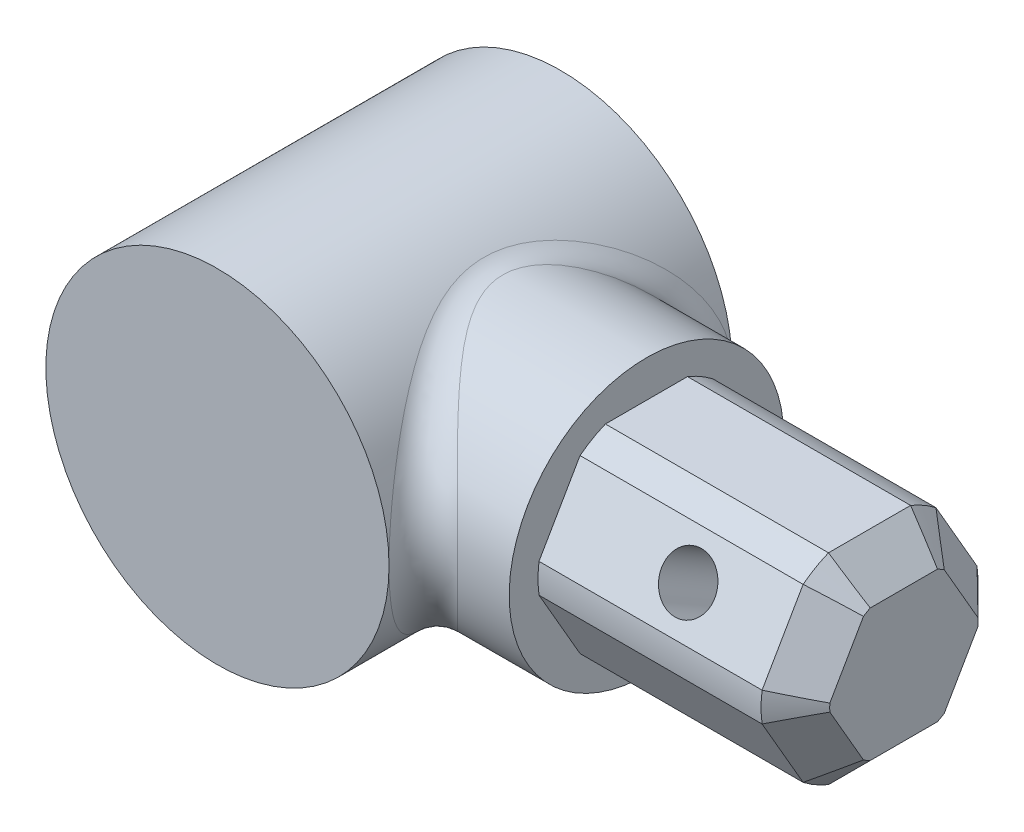
SolidWorks part; units mm, degrees
ref_plane "Front Plane" through (0, 0, 0) normal (0, 0, 1) x (1, 0, 0)
ref_plane "Top Plane" through (0, 0, 0) normal (0, 1, 0) x (1, 0, 0)
ref_plane "Right Plane" through (0, 0, 0) normal (1, 0, 0) x (0, 0, -1)
sketch "Sketch2" plane through (0, 0, 0) normal (0, 0, 1) x (1, 0, 0)
  circle A0 centre (0, 0) radius 10
  dimension "D1" = 20
extrude "Boss-Extrude1" add sketch "Sketch2" along normal blind 20
sketch "Sketch3" plane through (0, 0, 0) normal (1, 0, 0) x (0, 0, -1)
  line L0 (0, -10) -> (0, 10) construction
  line L1 (-20, 10) -> (-20, -10) construction
  line L2 (0, -10) -> (0, 10)
  line L3 (-20, 10) -> (-20, -10)
  line L4 (0, 0) -> (-20, 0) construction
  circle A0 centre (-10, 0) radius 8
  dimension "D1" = 16
extrude "Boss-Extrude2" add sketch "Sketch3" along normal blind 15 contours A0
sketch "Sketch4" plane through (15, 0, 0) normal (1, 0, 0) x (0, 0, -1)
  line L1 (-3.245, 0) -> (-6.6225, 5.85)
  line L2 (-6.6225, 5.85) -> (-13.3775, 5.85)
  line L3 (-13.3775, 5.85) -> (-16.755, 0)
  line L4 (-16.755, 0) -> (-13.3775, -5.85)
  line L5 (-13.3775, -5.85) -> (-6.6225, -5.85)
  line L6 (-6.6225, -5.85) -> (-3.245, 0)
  circle A0 centre (-10, 0) radius 6.32
  circle A1 centre (-10, 0) radius 5.85 construction
  dimension "D1" = 12.64
  dimension "D2" = 11.7
extrude "Boss-Extrude3" add sketch "Sketch4" along normal blind 15 contours L5 L6 L1 L2 L3 L4 region at (15, 0, 10)
fillet "Fillet1" radius 2 1 edges at (9.956, 0.9372, 2.0551)
chamfer "Chamfer1" distance 2 angle 45 12 edges at (30, -2.925, 15.0662) (30, 2.925, 15.0662) (30, 5.85, 10) (30, 2.925, 4.9338) (30, -2.925, 4.9338) (30, -5.85, 10) (30, 0, 3.68) (30, -5.4733, 6.84) (30, -5.4733, 13.16) (30, 0, 16.32) (30, 5.4733, 13.16) (30, 5.4733, 6.84)
ref_point "MountPoint (FreeJoint)"
ref_axis "Axis1" through (15, 0, 10) along (-1, 0, 0)
sketch "Sketch5" plane through (0, 7.2551, 12.5662) normal (0, 0.5, 0.866) x (1, 0, 0)
  line L0 (15, -2.6084) -> (15, -7.3916) construction
  circle A0 centre (22.5, -5) radius 1.55
  dimension "D1" = 3.1
  dimension "D2" = 7.5
extrude "Cut-Extrude1" cut sketch "Sketch5" against normal up to next
